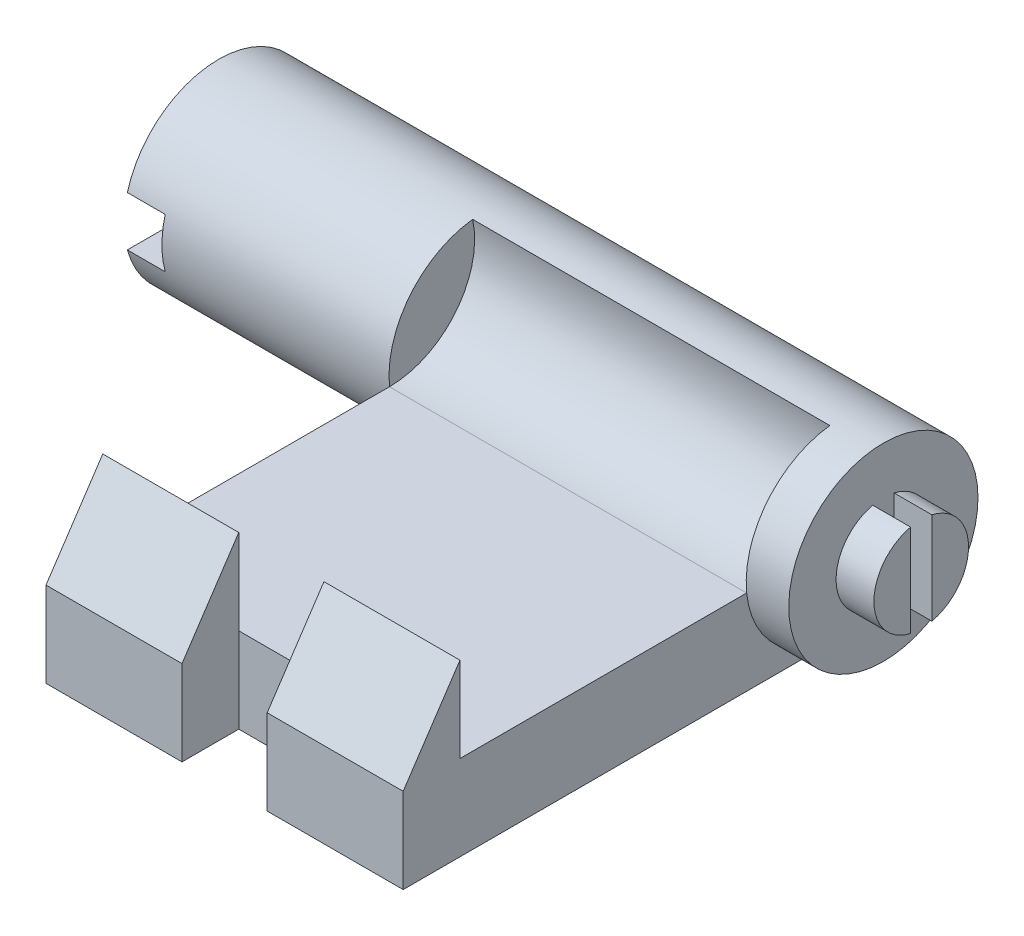
SolidWorks part; units mm, degrees
ref_plane "Front Plane" through (0, 0, 0) normal (0, 0, 1) x (1, 0, 0)
ref_plane "Top Plane" through (0, 0, 0) normal (0, 1, 0) x (1, 0, 0)
ref_plane "Right Plane" through (0, 0, 0) normal (1, 0, 0) x (0, 0, -1)
sketch "Sketch2" plane through (0, 0, 0) normal (1, 0, 0) x (0, 0, -1)
  line L0 (-81.788, 0) -> (-93.98, 0)
  line L1 (0, 0) -> (-81.788, 0)
  line L2 (0, 0) -> (0, 18.288)
  line L3 (0, 18.288) -> (-81.788, 18.288)
  line L4 (-81.788, 0) -> (-81.788, 18.288)
  line L5 (-93.98, 0) -> (-93.98, 18.288)
  line L6 (-93.98, 18.288) -> (-81.788, 36.576)
  line L7 (-81.788, 36.576) -> (-81.788, 18.288)
  arc A0 (0, 0) -> (-2.3567, 40.5029) centre (0, 20.32) ccw
  circle A1 centre (-20.2181, 36.576) radius 18.288
  point P12 (-20.2181, 18.288)
  dimension "D2" = 40.64
  dimension "D6" = 36.576
  dimension "D1" = 18.288
  dimension "D3" = 81.788
  dimension "D4" = 18.288
  dimension "D5" = 12.192
extrude "Boss-Extrude1" add sketch "Sketch2" along normal mid plane 76.708 contours L4 L1 L2 L3 | L7 L6 L5 L0 L4 | A1 L3 L2 A0 region at (0, 9.144, 40.894) region at (0, 14.224, 87.2067) region at (0, 21.0419, -6.7002)
sketch "Sketch3" plane through (38.354, 0, 0) normal (1, 0, 0) x (0, 0, -1)
  line L0 (-2.286, 30.2195) -> (-2.286, 10.4205)
  line L1 (0, 10.16) -> (0, 30.48) construction
  line L2 (2.286, 30.2195) -> (2.286, 10.4205)
  circle A0 centre (0, 20.32) radius 20.32
  circle A1 centre (0, 20.32) radius 10.16
  arc M8 (0, 0) -> (-2.3567, 40.5029) centre (0, 20.32) ccw
  arc M9 (-2.3567, 40.5029) -> (-20.2181, 18.288) centre (-20.2181, 36.576) cw
  dimension "D1" = 40.64
  dimension "D2" = 20.32
  dimension "D3" = 2.286
extrude "Boss-Extrude2" add sketch "Sketch3" along normal blind 9.144 contours A1 A0 M9 | A1 M9 | L0 A1 M9 | A1 A0 M9 M8 | L1 A1 L2 | A1 L1 L0 | L2 A1 region at (38.354, 20.32, 1.1381) region at (38.354, 30.6601, 2.8813) region at (38.354, 19.2533, 5.3181) region at (38.354, 20.32, -1.1381) region at (38.354, 25.8559, 6.8852) region at (38.354, 29.3957, 11.2878) region at (38.354, 20.32, -5.5712)
extrude "Boss-Extrude3" add sketch "Sketch3<3>" along normal blind 8.128 from surface contours L0 A1 M9 | L2 A1 | A1 M9 region at (38.354, 19.2533, 5.3181) region at (38.354, 20.32, -5.5712) region at (38.354, 25.8559, 6.8852) starting at face at (47.498, 20.32, -20.32)
sketch "Sketch3<3>" plane through (38.354, 0, 0) normal (1, 0, 0) x (0, 0, -1) same geometry as "Sketch3"
extrude "Boss-Extrude4" add sketch "Sketch3<4>" against normal blind 56.896 from vertex contours A1 A0 M9 | A1 A0 M9 M8 | L0 A1 M9 | L2 A1 | A1 M9 | A1 L1 L0 | L1 A1 L2 region at (38.354, 20.32, 1.1381) region at (38.354, 30.6601, 2.8813) region at (38.354, 19.2533, 5.3181) region at (38.354, 20.32, -1.1381) region at (38.354, 25.8559, 6.8852) region at (38.354, 29.3957, 11.2878) region at (38.354, 20.32, -5.5712) starting at point (-38.354, 40.5029, 2.3567)
sketch "Sketch3<4>" plane through (38.354, 0, 0) normal (1, 0, 0) x (0, 0, -1) same geometry as "Sketch3"
sketch "Sketch4" plane through (-95.25, 0, 0) normal (-1, 0, 0) x (0, 0, 1)
  line L0 (-20.32, 20.32) -> (20.32, 20.32) construction
  line L1 (-19.6074, 25.654) -> (19.6074, 25.654)
  line L2 (-19.6074, 14.986) -> (19.6074, 14.986)
  circle A0 centre (0, 20.32) radius 20.32 construction
  circle A1 centre (0, 20.32) radius 20.32
  circle M3 centre (0, 20.32) radius 20.32
  dimension "D2" = 40.64
  dimension "D1" = 5.334
extrude "Cut-Extrude1" cut sketch "Sketch4" against normal blind 8.128 contours L0 A1 L1 M3 | L0 A1 L2 M3 region at (-95.25, 22.9713, 0) region at (-95.25, 17.6687, 0)
sketch "Sketch5" plane through (0, 18.288, 0) normal (0, 1, 0) x (1, 0, 0)
  line L0 (0, -20.2181) -> (0, -93.98) construction
  line L1 (38.354, -20.2181) -> (-38.354, -20.2181) construction
  line L2 (38.354, -93.98) -> (-38.354, -93.98) construction
  line L3 (38.354, -81.788) -> (-38.354, -81.788) construction
  line L4 (-9.144, -81.788) -> (9.144, -81.788)
  line L5 (-9.144, -81.788) -> (-9.144, -93.98)
  line L6 (-9.144, -93.98) -> (9.144, -93.98)
  line L7 (9.144, -81.788) -> (9.144, -93.98)
  line L8 (-9.144, -87.884) -> (0, -87.884) construction
  line L9 (0, -87.884) -> (9.144, -87.884) construction
  line M8 (-38.354, -81.788) -> (38.354, -81.788)
  dimension "D1" = 18.288
extrude "Cut-Extrude3" cut sketch "Sketch5" against normal through all and the other way through all contours L7 L5 L6 M8 region at (0, 18.288, 87.884)
